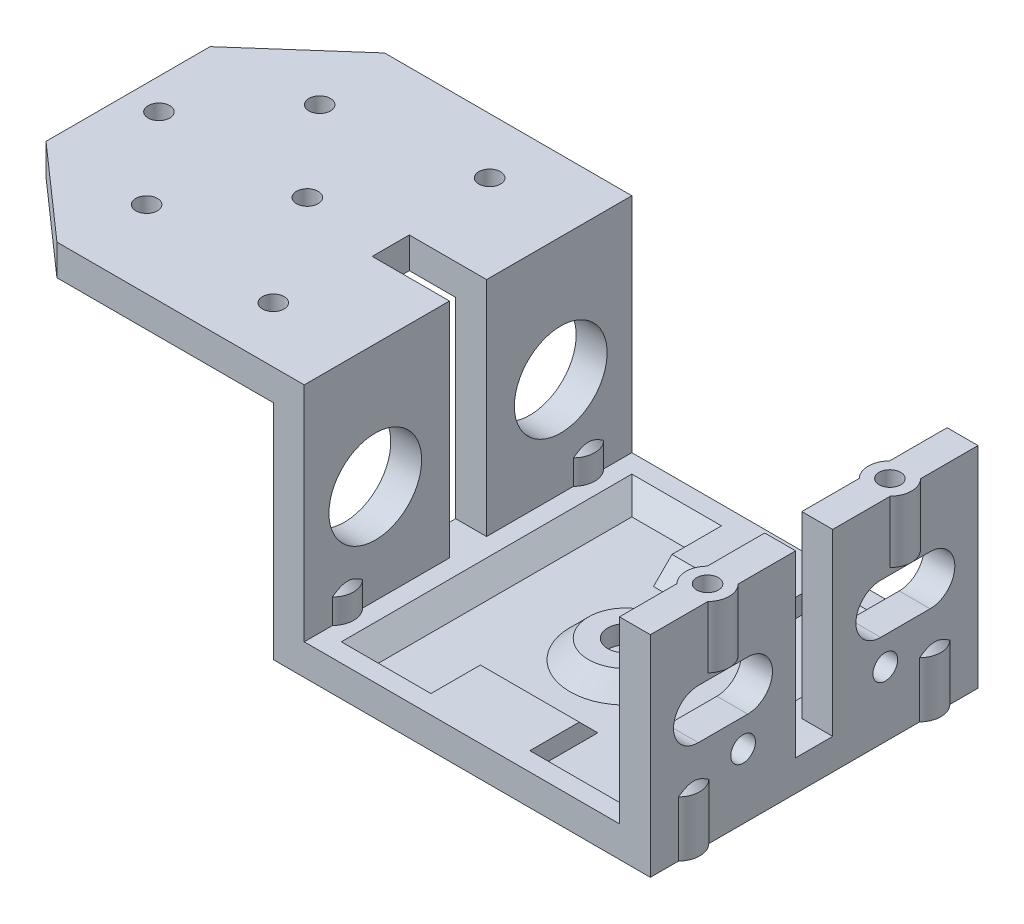
SolidWorks part; units mm, degrees
ref_plane "Ön Düzlem" through (0, 0, 0) normal (0, 0, 1) x (1, 0, 0)
ref_plane "Üst Düzlem" through (0, 0, 0) normal (0, 1, 0) x (1, 0, 0)
ref_plane "Sağ Düzlem" through (0, 0, 0) normal (1, 0, 0) x (0, 0, -1)
sketch "Çizim1" plane through (0, 0, 0) normal (0, 1, 0) x (1, 0, 0)
  line L1 (0, 0) -> (61, 0)
  line L2 (0, 0) -> (0, 53)
  line L3 (0, 53) -> (61, 53)
  line L4 (61, 0) -> (61, 53)
  dimension "D1" = 53
  dimension "D2" = 61
extrude "Yükseklik-Ekstrüzyon1" add sketch "Çizim1" along normal blind 5
sketch "Çizim2" plane through (0, 5, 0) normal (0, 1, 0) x (1, 0, 0)
  line L0 (0, 0) -> (61, 0) construction
  line L1 (0, 53) -> (5, 53)
  line L2 (0, 53) -> (0, 0)
  line L3 (0, 0) -> (5, 0)
  line L4 (5, 53) -> (5, 0)
  dimension "D1" = 5
extrude "Yükseklik-Ekstrüzyon2" add sketch "Çizim2" along normal blind 36
sketch "Çizim3" plane through (0, 0, 0) normal (-1, 0, 0) x (0, 0, 1)
  line L0 (0, 41) -> (0, 0) construction
  line L1 (-53, 41) -> (0, 41)
  line L2 (-53, 41) -> (-53, 36)
  line L3 (-53, 36) -> (0, 36)
  line L4 (0, 41) -> (0, 36)
  dimension "D1" = 5
extrude "Yükseklik-Ekstrüzyon3" add sketch "Çizim3" along normal blind 50
sketch "Çizim4" plane through (0, 5, 0) normal (0, 1, 0) x (1, 0, 0)
  line L0 (5, 0) -> (61, 0) construction
  line L1 (61, 53) -> (56, 53)
  line L2 (61, 53) -> (61, 0)
  line L3 (61, 0) -> (56, 0)
  line L4 (56, 53) -> (56, 0)
  dimension "D1" = 5
extrude "Yükseklik-Ekstrüzyon4" add sketch "Çizim4" along normal blind 29
sketch "Çizim5" plane through (0, 41, 0) normal (0, 1, 0) x (1, 0, 0)
  line L0 (-35, 53) -> (-50, 39.7712)
  line L1 (5, 53) -> (-50, 53) construction
  line L2 (-50, 0) -> (-50, 53) construction
  line L3 (-50, 39.7712) -> (-50, 53)
  line L4 (-50, 53) -> (-35, 53)
  line L5 (-35, 53) -> (-35.1142, 53.0528)
  line L6 (-50, 26.5) -> (-12.0331, 26.5) construction
  line L7 (-35, 0) -> (-35.1142, -0.0528)
  line L8 (-50, 0) -> (-35, 0)
  line L9 (-50, 13.2288) -> (-50, 0)
  line L10 (-35, 0) -> (-50, 13.2288)
  line M4 (5, 53) -> (-50, 53)
  line M5 (-50, 53) -> (-50, 0)
  line M6 (-50, 0) -> (5, 0)
  dimension "D1" = 20
  dimension "D2" = 15
extrude "Kes-Ekstrüzyon1" cut sketch "Çizim5" against normal blind 29 contours L0 M4 M5 | L10 M6 M5 region at (-45, 41, -4.4096) region at (-45, 41, -48.5904)
sketch "Çizim6" plane through (0, 5, 0) normal (0, 1, 0) x (1, 0, 0)
  line L0 (30.5, 53) -> (30.5, 29.05) construction
  line L1 (7, 51) -> (54, 51)
  line L2 (7, 51) -> (7, 2)
  line L3 (7, 2) -> (54, 2)
  line L4 (54, 51) -> (54, 2)
  line L5 (56, 53) -> (5, 53) construction
  line L6 (5, 0) -> (56, 0) construction
  line L7 (5, 0) -> (5, 53) construction
  dimension "D1" = 2
  dimension "D2" = 2
  dimension "D3" = 2
extrude "Kes-Ekstrüzyon2" cut sketch "Çizim6" against normal blind 3
sketch "Çizim7" plane through (0, 2, 0) normal (0, 1, 0) x (1, 0, 0)
  line L0 (30.5, 51) -> (30.5, 2) construction
  line L1 (54, 51) -> (7, 51) construction
  line L2 (7, 2) -> (54, 2) construction
  line L3 (7, 26.5) -> (54, 26.5) construction
  line L4 (7, 51) -> (7, 2) construction
  line L5 (54, 2) -> (54, 51) construction
  circle A0 centre (30.5, 26.5) radius 2.9
  circle A1 centre (30.5, 26.5) radius 5
  dimension "D1" = 5.8
  dimension "D2" = 10
extrude "Yükseklik-Ekstrüzyon5" add sketch "Çizim7" along normal blind 4
chamfer "Pah2" distance 4 angle 45 4 edges at (30.5, 2, -2) (54, 2, -26.5) (7, 2, -26.5) (30.5, 2, -51)
sketch "Çizim8" plane through (61, 0, 0) normal (1, 0, 0) x (0, 0, -1)
  line L0 (0, 41) -> (53, 41) construction
  line L1 (23.5, 5) -> (29.5, 5)
  line L2 (23.5, 5) -> (23.5, 41)
  line L3 (23.5, 41) -> (29.5, 41)
  line L4 (29.5, 5) -> (29.5, 41)
  line L5 (0, 0) -> (53, 0) construction
  line L6 (26.5, 0) -> (26.5, 18.9918) construction
  point P8 (26.5, 0)
  dimension "D1" = 5
  dimension "D2" = 6
extrude "Kes-Ekstrüzyon4" cut sketch "Çizim8" against normal up to vertex (61 mm away) up to point (0, 0, -53)
sketch "Çizim9" plane through (0, 41, 0) normal (0, 1, 0) x (1, 0, 0)
  line L0 (0, 29.5) -> (5, 29.5) construction
  line L1 (5, 23.5) -> (-7.5, 23.5)
  line L2 (5, 23.5) -> (5, 29.5)
  line L3 (5, 29.5) -> (-7.5, 29.5)
  line L4 (-7.5, 23.5) -> (-7.5, 29.5)
  dimension "D1" = 12.5
extrude "Kes-Ekstrüzyon5" cut sketch "Çizim9" against normal blind 5
sketch "Çizim11" plane through (0, 0, 0) normal (0, 0, 1) x (1, 0, 0)
  line L1 (5, 5) -> (56, 5)
  line L2 (5, 5) -> (5, 34)
  line L3 (5, 34) -> (56, 34)
  line L4 (56, 5) -> (56, 34)
extrude "Kes-Ekstrüzyon7" cut sketch "Çizim11" against normal up to vertex (53 mm away) up to point (5, 5, -53)
chamfer "Pah3" distance 4 angle 45 1 edges at (30.5, 2, -21.5)
sketch "Çizim12" plane through (0, 0, 0) normal (0, -1, 0) x (1, 0, 0)
  line L0 (0, -26.5) -> (61, -26.5) construction
  line L1 (0, -53) -> (0, 0) construction
  line L2 (61, 0) -> (61, -53) construction
  line L3 (2.5, 0) -> (2.5, -53) construction
  line L4 (0, 0) -> (61, 0) construction
  line L5 (61, -53) -> (0, -53) construction
  line L6 (0, -23.5) -> (0, 0) construction
  line L7 (30.5, 0) -> (30.5, -53) construction
  circle A0 centre (2.5, -7) radius 1.75
  circle A1 centre (2.5, -46) radius 1.75
  circle A2 centre (58.5, -7) radius 1.75
  circle A3 centre (58.5, -46) radius 1.75
  dimension "D2" = 3.5
  dimension "D1" = 2.5
  dimension "D3" = 7
extrude "Kes-Ekstrüzyon8" cut sketch "Çizim12" against normal blind 12
sketch "Çizim13" plane through (0, 0, 0) normal (0, -1, 0) x (1, 0, 0)
  circle A0 centre (2.5, -7) radius 2
  circle A1 centre (2.5, -7) radius 3.5
  circle A2 centre (58.5, -7) radius 2
  circle A3 centre (58.5, -7) radius 3.5
  circle A4 centre (58.5, -46) radius 2
  circle A5 centre (58.5, -46) radius 3.5
  circle A6 centre (2.5, -46) radius 2
  circle A7 centre (2.5, -46) radius 3.5
  dimension "D1" = 4
  dimension "D2" = 7
  dimension "D3" = 4
  dimension "D4" = 4
  dimension "D5" = 4
  dimension "D6" = 7
  dimension "D7" = 7
  dimension "D8" = 7
extrude "Yükseklik-Ekstrüzyon6" add sketch "Çizim13" against normal blind 10
chamfer "Pah4" distance 1 angle 45 1 edges at (62, 10, -7)
chamfer "Pah5" distance 1 angle 45 7 edges at (6, 10, -46) (6, 10, -7) (55, 10, -7) (55, 10, -46) (-1, 10, -46) (-1, 10, -7) (62, 10, -46)
sketch "Çizim14" plane through (0, 34, 0) normal (0, 1, 0) x (1, 0, 0)
  line L0 (58.5, 53) -> (58.5, 0) construction
  line L1 (61, 53) -> (56, 53) construction
  line L2 (56, 0) -> (61, 0) construction
  line L3 (61, 41.25) -> (56, 41.25) construction
  line L4 (61, 29.5) -> (61, 53) construction
  line L5 (56, 53) -> (56, 29.5) construction
  line L6 (61, 11.75) -> (56, 11.75) construction
  line L7 (61, 0) -> (61, 23.5) construction
  line L8 (56, 23.5) -> (56, 0) construction
  circle A0 centre (58.5, 41.25) radius 1.75
  circle A1 centre (58.5, 11.75) radius 1.75
  dimension "D1" = 3.5
  dimension "D2" = 3.5
extrude "Kes-Ekstrüzyon9" cut sketch "Çizim14" against normal blind 10
sketch "Çizim15" plane through (0, 34, 0) normal (0, 1, 0) x (1, 0, 0)
  circle A0 centre (58.5, 11.75) radius 2
  circle A1 centre (58.5, 41.25) radius 2
  circle A2 centre (58.5, 41.25) radius 3.5
  circle A3 centre (58.5, 11.75) radius 3.5
  dimension "D1" = 4
  dimension "D2" = 4
  dimension "D3" = 7
  dimension "D4" = 7
extrude "Yükseklik-Ekstrüzyon7" add sketch "Çizim15" against normal blind 10
sketch "Çizim16" plane through (0, 36, 0) normal (0, -1, 0) x (1, 0, 0)
  line L0 (-50, -26.5) -> (-7.5, -26.5) construction
  line L1 (-50, -39.7712) -> (-50, -13.2288) construction
  line L2 (-7.5, -29.5) -> (-7.5, -23.5) construction
  line L3 (-33, 0) -> (-33, -53) construction
  line L4 (-35, 0) -> (0, 0) construction
  line L5 (-35, -53) -> (0, -53) construction
  circle A0 centre (-33, -12.5) radius 1.75
  circle A1 centre (-33, -40.5) radius 1.75
  circle A2 centre (-21, -26.5) radius 1.75
  circle A3 centre (-45, -26.5) radius 1.75
  dimension "D2" = 3.5
  dimension "D3" = 3.5
  dimension "D4" = 3.5
  dimension "D5" = 3.5
  dimension "D1" = 17
  dimension "D6" = 28
  dimension "D7" = 24
extrude "Kes-Ekstrüzyon10" cut sketch "Çizim16" against normal blind 10
sketch "Çizim17" plane through (0, 41, 0) normal (0, 1, 0) x (1, 0, 0)
  line L0 (-9, 65.336) -> (-9, -9.7559) construction
  line L1 (5, 29.5) -> (5, 53) construction
  line L2 (-50, 26.5) -> (78.321, 26.5) construction
  line L3 (-50, 13.2288) -> (-50, 39.7712) construction
  circle A0 centre (-9, 44) radius 1.75
  circle A1 centre (-9, 9) radius 1.75
  dimension "D2" = 3.5
  dimension "D3" = 3.5
  dimension "D1" = 14
  dimension "D4" = 35
extrude "Kes-Ekstrüzyon11" cut sketch "Çizim17" against normal blind 10
sketch "Çizim18" plane through (61, 0, 0) normal (1, 0, 0) x (0, 0, -1)
  line L0 (-12.0525, 10.5) -> (55.5768, 10.5) construction
  line L1 (9.4495, 0) -> (43.5505, 0) construction
  line L2 (26.5, 0) -> (26.5, 20.1364) construction
  circle A0 centre (15, 10.5) radius 2
  circle A1 centre (38, 10.5) radius 2
  point P7 (26.5, 0)
  dimension "D3" = 4
  dimension "D4" = 4
  dimension "D1" = 10.5
  dimension "D2" = 23
extrude "Kes-Ekstrüzyon12" cut sketch "Çizim18" against normal blind 10
sketch "Çizim23" plane through (0, 0, 0) normal (-1, 0, 0) x (0, 0, 1)
  line L0 (-53, 36) -> (-29.5, 36) construction
  line L1 (-26.5, 0) -> (-26.5, 32.734) construction
  line L2 (-43.5505, 0) -> (-9.4495, 0) construction
  circle A0 centre (-41.5, 21) radius 7.5
  circle A1 centre (-11.5, 21) radius 7.5
  dimension "D1" = 15
  dimension "D2" = 15
  dimension "D3" = 15
  dimension "D4" = 30
extrude "Kes-Ekstrüzyon17" cut sketch "Çizim23" against normal blind 11
sketch "Çizim24" plane through (61, 0, 0) normal (1, 0, 0) x (0, 0, -1)
  line L0 (15.75, 19) -> (7.75, 19) construction
  line L1 (15.75, 15) -> (7.75, 15)
  line L2 (15.75, 23) -> (7.75, 23)
  line L3 (0, 34) -> (0, 0) construction
  line L5 (9.4495, 0) -> (43.5505, 0) construction
  line L6 (26.5, 0) -> (26.5, -11.3884) construction
  line L7 (37.25, 19) -> (45.25, 19) construction
  line L8 (37.25, 15) -> (45.25, 15)
  line L9 (37.25, 23) -> (45.25, 23)
  arc A0 (15.75, 15) -> (15.75, 23) centre (15.75, 19) ccw
  arc A1 (7.75, 23) -> (7.75, 15) centre (7.75, 19) ccw
  arc A2 (37.25, 15) -> (37.25, 23) centre (37.25, 19) cw
  arc A3 (45.25, 23) -> (45.25, 15) centre (45.25, 19) cw
  point P2 (11.75, 19)
  point P15 (41.25, 19)
  dimension "D1" = 11.75
  dimension "D2" = 8
  dimension "D3" = 8
  dimension "D4" = 19
extrude "Kes-Ekstrüzyon18" cut sketch "Çizim24" against normal blind 10
sketch "Çizim25" plane through (0, 5, 0) normal (0, 1, 0) x (1, 0, 0)
  line L0 (8, 50) -> (53, 50) construction
  line L1 (22.5, 50) -> (38.5, 50)
  line L2 (22.5, 50) -> (22.5, 38)
  line L3 (22.5, 38) -> (38.5, 38)
  line L4 (38.5, 50) -> (38.5, 38)
  line L5 (53, 3) -> (8, 3) construction
  line L6 (22.5, 3) -> (38.5, 3)
  line L7 (22.5, 3) -> (22.5, 15)
  line L8 (22.5, 15) -> (38.5, 15)
  line L9 (38.5, 3) -> (38.5, 15)
  line L10 (30.5, 26.5) -> (30.5, 61.0535) construction
  dimension "D1" = 12
  dimension "D2" = 12
  dimension "D3" = 16
  dimension "D4" = 16
extrude "Yükseklik-Ekstrüzyon8" add sketch "Çizim25" against normal up to vertex (3 mm away) up to point (11, 2, -6)
chamfer "Pah6" distance 4 angle 45 2 edges at (30.5, 5, -38) (30.5, 5, -15)
